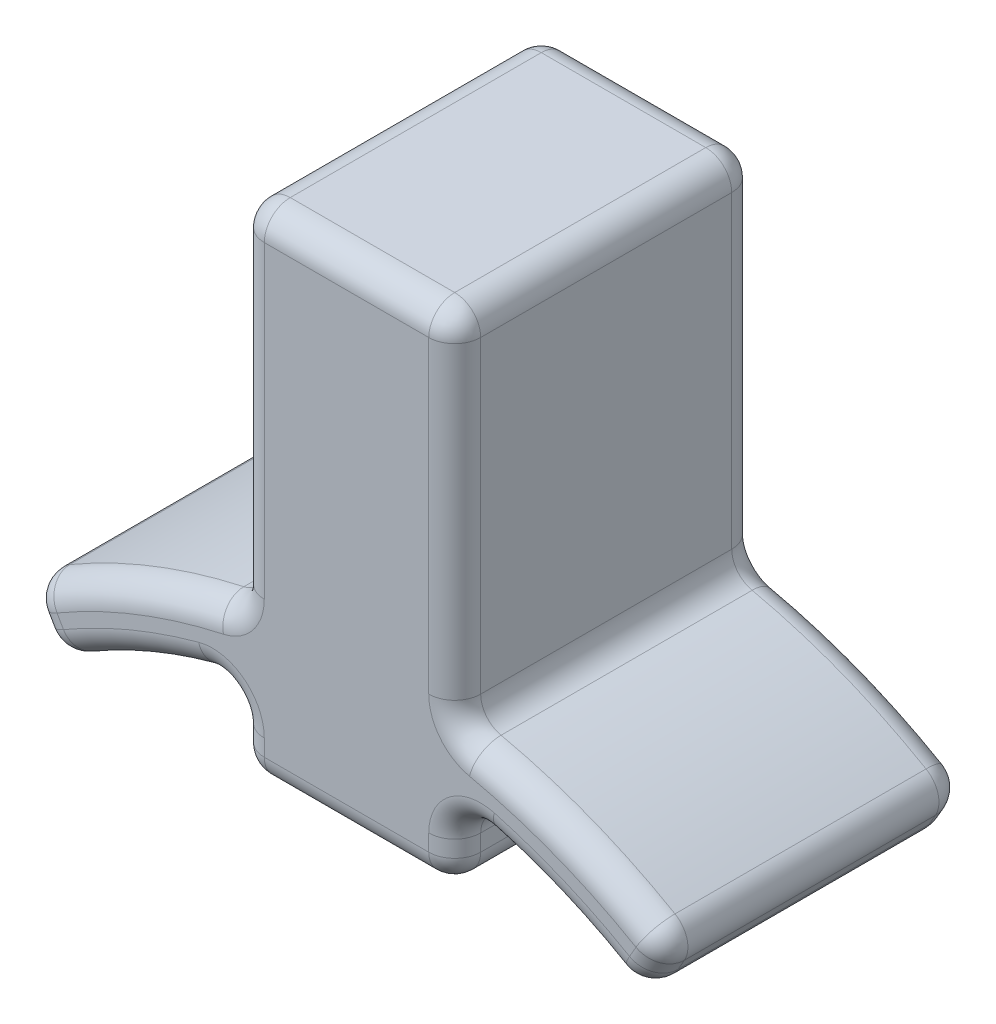
SolidWorks part; units mm, degrees
ref_plane "前视基准面" through (0, 0, 0) normal (0, 0, 1) x (1, 0, 0)
ref_plane "上视基准面" through (0, 0, 0) normal (0, 1, 0) x (1, 0, 0)
ref_plane "右视基准面" through (0, 0, 0) normal (1, 0, 0) x (0, 0, -1)
other "Configuration Table"
ref_axis "基准轴1" through (0, -46.8641, 0) along (0, 1, 0)
sketch "草图1" plane through (0, 0, 0) normal (0, 0, 1) x (1, 0, 0)
  line L0 (-2.5, 0) -> (2.5, 0)
  line L1 (2.5, 0) -> (2.5, 11.4982)
  line L2 (2.5, 11.4982) -> (-2.5, 11.4982)
  line L3 (-2.5, 11.4982) -> (-2.5, 0)
  line L4 (-6.75, 0) -> (-7.5, 1.299)
  line L5 (6.75, 0) -> (7.5, 1.299)
  line L6 (0, 0) -> (0, 11.4982) construction
  arc A0 (-6.75, 0) -> (6.75, 0) centre (0, -10.3906) cw
  arc A1 (7.5, 1.299) -> (-7.5, 1.299) centre (0, -10.3906) ccw
  point P3 (0, 0)
  point P19 (0, 2)
  point P20 (0, 3.4982)
  dimension "D2" = 15
  dimension "D1" = 5
  dimension "D3" = 1.5
  dimension "D4" = 60
  dimension "D5" = 2
  dimension "D6" = 8
extrude "凸台-拉伸1" add sketch "草图1" along normal mid plane 7 contours L6 A1 L1 L2 | A1 L6 L2 L3 | L3 A1 L4 A0 | A0 L6 A1 L3 | L6 A0 L1 A1 | L0 L6 A0 L3 | L6 L0 L1 A0 | L5 A1 L1 A0 region at (-1.2223, 0.9592, 0) region at (1.2223, 0.9592, 0) region at (-4.8768, 1.7455, 0) region at (-1.2538, 2.6687, 0) region at (1.2538, 2.6687, 0) region at (-1.2558, 7.4602, 0) region at (4.8768, 1.7455, 0) region at (1.2558, 7.4602, 0)
sketch "草图2" plane through (0, 0, 0) normal (0, -1, 0) x (1, 0, 0)
  line L1 (-0.55, 1) -> (0.55, 1)
  line L2 (-0.55, 1) -> (-0.55, -1)
  line L3 (-0.55, -1) -> (0.55, -1)
  line L4 (0.55, 1) -> (0.55, -1)
  line L5 (-0.55, 1) -> (0.55, -1) construction
  line L6 (-0.55, -1) -> (0.55, 1) construction
  point P0 (0, 0)
  dimension "D1" = 1.1
  dimension "D2" = 2
extrude "切除-拉伸1" cut sketch "草图2" against normal blind 4.5
fillet "圆角1" radius 0.6 36 edges at (2.5, 0, 0) (2.5, 1.7452, 0) (-2.5, 1.7452, 0) (-2.5, 0, 0) (2.5, 11.4982, 0) (-2.5, 11.4982, 0) (-5.0963, 2.5294, -3.5) (-4.7066, 1.0713, -3.5) (-2.5, 0.8726, -3.5) (0, 0, -3.5) (2.5, 0.8726, -3.5) (4.7066, 1.0713, -3.5) (5.0963, 2.5294, -3.5) (2.5, 7.3847, -3.5) (0, 11.4982, -3.5) (-2.5, 7.3847, -3.5) (0, 11.4982, 3.5) (2.5, 7.3847, 3.5) (5.0963, 2.5294, 3.5) (4.7066, 1.0713, 3.5) (2.5, 0.8726, 3.5) (0, 0, 3.5) (-2.5, 0.8726, 3.5) (-4.7066, 1.0713, 3.5) (-5.0963, 2.5294, 3.5) (-2.5, 7.3847, 3.5) (-7.5, 1.299, 0) (-7.125, 0.6495, 3.5) (-6.75, 0, 0) (-7.125, 0.6495, -3.5) (6.75, 0, 0) (7.125, 0.6495, 3.5) (7.5, 1.299, 0) (7.125, 0.6495, -3.5) (2.5, 3.2713, 0) (-2.5, 3.2713, 0)
fillet "圆角2" radius 0.2 4 edges at (0.55, 0, 0) (-0.55, 0, 0) (0, 0, -1) (0, 0, 1)
